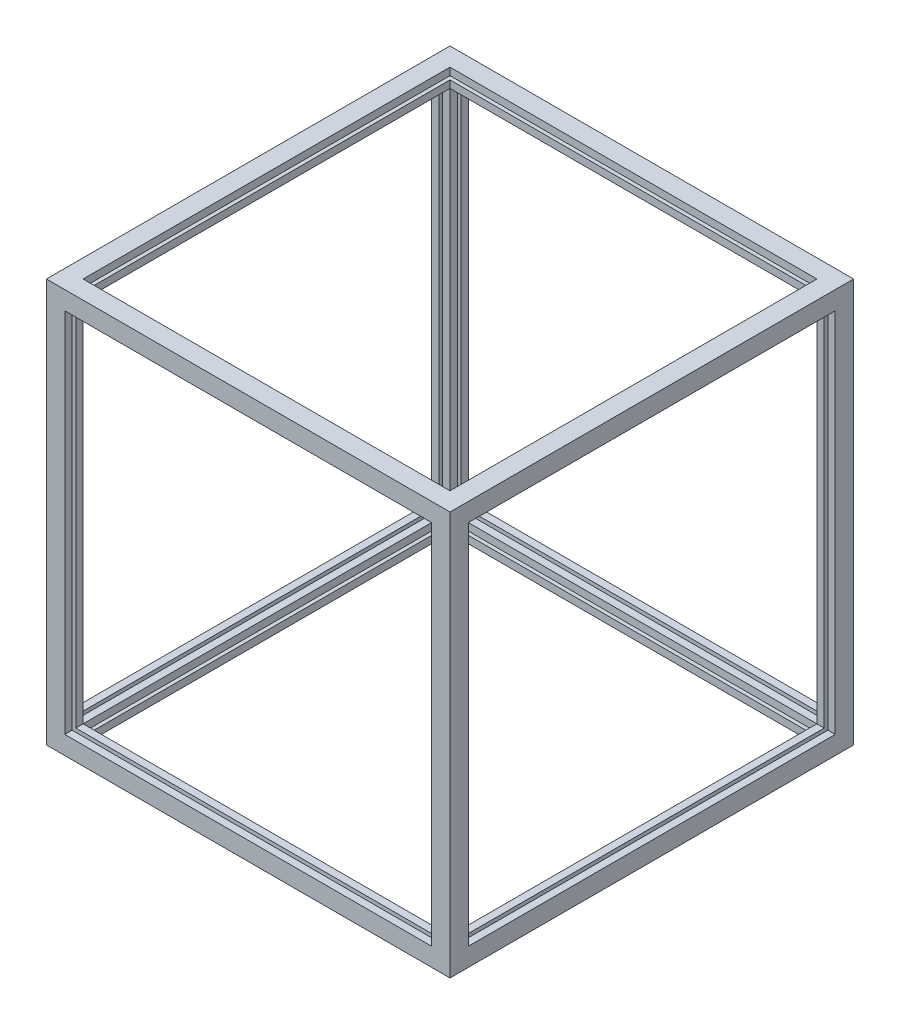
SolidWorks part; units mm, degrees
ref_plane "Alzado" through (0, 0, 0) normal (0, 0, 1) x (1, 0, 0)
ref_plane "Planta" through (0, 0, 0) normal (0, 1, 0) x (1, 0, 0)
ref_plane "Vista lateral" through (0, 0, 0) normal (1, 0, 0) x (0, 0, -1)
sketch "Croquis1" plane through (0, 0, 0) normal (0, 0, 1) x (1, 0, 0)
  line L0 (10, 10) -> (10, 210)
  line L1 (0, 0) -> (220, 0)
  line L2 (0, 0) -> (0, 220)
  line L3 (0, 220) -> (220, 220)
  line L4 (220, 0) -> (220, 220)
  line L5 (10, 210) -> (210, 210)
  line L6 (210, 10) -> (210, 210)
  line L7 (10, 10) -> (210, 10)
  dimension "D2" = 220
  dimension "D3" = 220
  dimension "D1" = 10
extrude "MarcoBase" add sketch "Croquis1" along normal blind 10
sketch "Croquis2" plane through (0, 0, 10) normal (0, 0, 1) x (1, 0, 0)
  line L1 (0, 220) -> (10, 220)
  line L2 (0, 220) -> (0, 210)
  line L3 (0, 210) -> (10, 210)
  line L4 (10, 220) -> (10, 210)
  line L5 (220, 220) -> (210, 220)
  line L6 (220, 220) -> (220, 210)
  line L7 (220, 210) -> (210, 210)
  line L8 (210, 220) -> (210, 210)
  line L9 (220, 0) -> (210, 0)
  line L10 (220, 0) -> (220, 10)
  line L11 (220, 10) -> (210, 10)
  line L12 (210, 0) -> (210, 10)
  line L13 (0, 0) -> (10, 0)
  line L14 (0, 0) -> (0, 10)
  line L15 (0, 10) -> (10, 10)
  line L16 (10, 0) -> (10, 10)
extrude "Pilares" add sketch "Croquis2" along normal blind 210
sketch "Croquis3" plane through (0, 0, 220) normal (0, 0, 1) x (1, 0, 0)
  line L0 (10, 210) -> (10, 10)
  line L1 (0, 220) -> (220, 220)
  line L2 (0, 220) -> (0, 0)
  line L3 (0, 0) -> (220, 0)
  line L4 (220, 220) -> (220, 0)
  line L5 (10, 10) -> (210, 10)
  line L6 (210, 210) -> (210, 10)
  line L7 (10, 210) -> (210, 210)
  dimension "D1" = 10
extrude "Exterior" add sketch "Croquis3" against normal blind 10
ref_plane "PlanoX" through (0, 0, 110) normal (0, 0, 1) x (1, 0, 0)
ref_plane "PlanoY" through (110, 0, 0) normal (1, 0, 0) x (0, 0, -1)
ref_plane "PlanoZ" through (0, 110, 0) normal (0, 1, 0) x (1, 0, 0)
ref_axis "EjeXY" through (110, 262.5, 110) along (0, -1, 0)
ref_axis "EjeXZ" through (262.5, 110, 110) along (-1, 0, 0)
sketch "Croquis6" plane through (0, 0, 0) normal (0, 0, -1) x (-1, 0, 0)
  line L0 (-220, 110) -> (0, 110) construction
  line L1 (-220, 0) -> (-220, 220) construction
  line L2 (0, 220) -> (0, 0) construction
  line L3 (-110, 137.5) -> (-110, -137.5) construction
  line L5 (-220, 118) -> (-120, 118)
  line L6 (-220, 118) -> (-220, 102)
  line L7 (-220, 102) -> (-120, 102)
  line L8 (-120, 118) -> (-120, 102)
  line L9 (0, 102) -> (-100, 102)
  line L10 (-100, 118) -> (-100, 102)
  line L11 (0, 118) -> (-100, 118)
  line L12 (0, 118) -> (0, 102)
  circle A0 centre (-75, 110) radius 3.175
  circle A1 centre (-145, 110) radius 3.175
  point P8 (-110, 110)
  dimension "D2" = 6.35
  dimension "D1" = 35
  dimension "D3" = 8
  dimension "D4" = 16
  dimension "D5" = 100
sketch "Croquis8" plane through (0, 0, 10) normal (0, 0, 1) x (1, 0, 0)
  line L0 (0, 0) -> (10, 10) construction
  line L3 (210, 10) -> (220, 0) construction
  line L4 (220, 220) -> (210, 210) construction
  line L21 (0, 220) -> (10, 210) construction
  line L26 (216, 216) -> (4, 216)
  line L27 (4, 216) -> (4, 4)
  line L28 (4, 4) -> (216, 4)
  line L29 (216, 4) -> (216, 216)
  line L30 (214, 214) -> (6, 214)
  line L31 (6, 214) -> (6, 6)
  line L32 (6, 6) -> (214, 6)
  line L33 (214, 6) -> (214, 214)
extrude "Cortar-Extruir5" cut sketch "Croquis8" against normal blind 5 contours L26 L27 L28 L29 | L30 L31 L32 L33
pattern_circular "MatrizC1" count 4 over 360 about axis through (262.5, 110, 110) along (-1, 0, 0) of "Cortar-Extruir5"
pattern_circular "MatrizC2" count 4 over 360 about axis through (110, 262.5, 110) along (0, -1, 0) of "Cortar-Extruir5"
